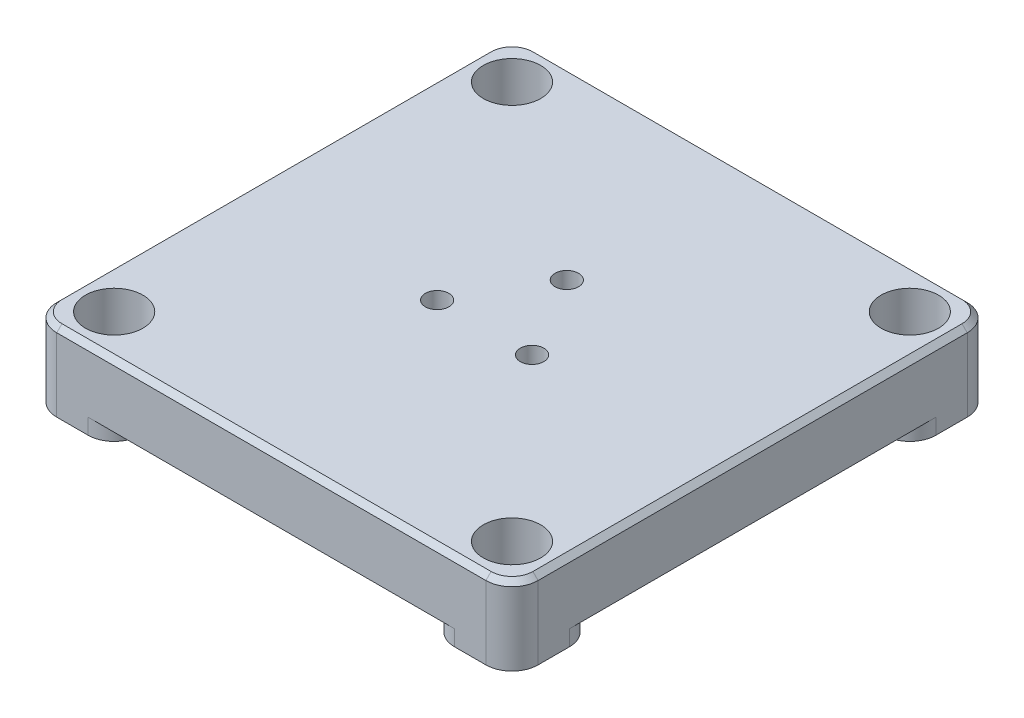
SolidWorks part; units mm, degrees
ref_plane "Спереди" through (0, 0, 0) normal (0, 0, 1) x (1, 0, 0)
ref_plane "Сверху" through (0, 0, 0) normal (0, 1, 0) x (1, 0, 0)
ref_plane "Справа" through (0, 0, 0) normal (1, 0, 0) x (0, 0, -1)
sketch "Эскиз1" plane through (0, 0, 0) normal (0, 1, 0) x (1, 0, 0)
  line L1 (-46.1, 46.1) -> (46.1, 46.1)
  line L2 (-46.1, 46.1) -> (-46.1, -46.1)
  line L3 (-46.1, -46.1) -> (46.1, -46.1)
  line L4 (46.1, 46.1) -> (46.1, -46.1)
  line L5 (-46.1, 46.1) -> (46.1, -46.1) construction
  line L6 (-46.1, -46.1) -> (46.1, 46.1) construction
  line L7 (38.1, 38.1) -> (-38.1, 38.1) construction
  line L8 (38.1, 38.1) -> (38.1, -38.1) construction
  line L9 (38.1, -38.1) -> (-38.1, -38.1) construction
  line L10 (-38.1, 38.1) -> (-38.1, -38.1) construction
  line L11 (38.1, 38.1) -> (-38.1, -38.1) construction
  line L12 (38.1, -38.1) -> (-38.1, 38.1) construction
  circle A0 centre (0, 0) radius 10.5 construction
  circle A1 centre (0, 10.5) radius 2.25
  circle A2 centre (-38.1, 38.1) radius 3.5
  circle A3 centre (38.1, 38.1) radius 3.5
  circle A4 centre (38.1, -38.1) radius 3.5
  circle A5 centre (-38.1, -38.1) radius 3.5
  circle A6 centre (9.0933, -5.25) radius 2.25
  circle A7 centre (-9.0933, -5.25) radius 2.25
  point P0 (0, 0)
  point P6 (0, 0)
  dimension "D4" = 21
  dimension "D5" = 4.5
  dimension "D6" = 7
  dimension "D7" = 7
  dimension "D8" = 7
  dimension "D9" = 7
  dimension "D1" = 92.2
  dimension "D2" = 92.2
  dimension "D3" = 76.2
  dimension "D10" = 3
extrude "Бобышка-Вытянуть1" add sketch "Эскиз1" along normal blind 12
sketch "Эскиз2" plane through (0, 0, 0) normal (0, -1, 0) x (1, 0, 0)
  circle A0 centre (-9.0933, 5.25) radius 3.6
  circle A1 centre (9.0933, 5.25) radius 3.6
  circle A2 centre (0, -10.5) radius 3.6
  dimension "D1" = 7.2
  dimension "D2" = 7.2
  dimension "D3" = 7.2
extrude "Вырез-Вытянуть1" cut sketch "Эскиз2" against normal offset from surface (2 mm away) 10 up to face at (9.0933, 12, 7.5)
sketch "Эскиз3" plane through (0, 0, 0) normal (0, -1, 0) x (1, 0, 0)
  line L0 (30.1, 30.1) -> (46.1, 30.1)
  line L1 (-30.1, 30.1) -> (-46.1, 30.1)
  line L2 (-30.1, 30.1) -> (-30.1, 46.1)
  line L3 (-30.1, 46.1) -> (-46.1, 46.1)
  line L4 (-46.1, 30.1) -> (-46.1, 46.1)
  line L5 (-30.1, 30.1) -> (-46.1, 46.1) construction
  line L6 (-30.1, 46.1) -> (-46.1, 30.1) construction
  line L7 (30.1, 30.1) -> (30.1, 46.1)
  line L8 (30.1, 46.1) -> (46.1, 46.1)
  line L9 (46.1, 30.1) -> (46.1, 46.1)
  line L10 (30.1, -30.1) -> (30.1, -46.1)
  line L11 (30.1, -30.1) -> (46.1, -30.1)
  line L12 (46.1, -30.1) -> (46.1, -46.1)
  line L13 (30.1, -46.1) -> (46.1, -46.1)
  line L14 (-30.1, -30.1) -> (-46.1, -30.1)
  line L15 (-30.1, -30.1) -> (-30.1, -46.1)
  line L16 (-30.1, -46.1) -> (-46.1, -46.1)
  line L17 (-46.1, -30.1) -> (-46.1, -46.1)
  line L18 (46.1, 46.1) -> (46.1, -46.1) construction
  line L19 (-46.1, 46.1) -> (46.1, 46.1) construction
  circle A0 centre (-38.1, 38.1) radius 3.5
  circle A1 centre (38.1, 38.1) radius 3.5
  circle A2 centre (38.1, -38.1) radius 3.5
  circle A3 centre (-38.1, -38.1) radius 3.5
  circle A4 centre (38.1, 38.1) radius 3.5 construction
  point P0 (-38.1, 38.1)
  dimension "D1" = 4
  dimension "D2" = 4
extrude "Бобышка-Вытянуть2" add sketch "Эскиз3" along normal blind 3
sketch "Эскиз4" plane through (0, 12, 0) normal (0, 1, 0) x (1, 0, 0)
  circle A0 centre (38.1, 38.1) radius 5.5
  circle A1 centre (38.1, -38.1) radius 5.5
  circle A2 centre (-38.1, -38.1) radius 5.5
  circle A3 centre (-38.1, 38.1) radius 5.5
  circle A4 centre (-38.1, 38.1) radius 3.5 construction
  dimension "D1" = 11
  dimension "D2" = 4
extrude "Вырез-Вытянуть2" cut sketch "Эскиз4" against normal offset from surface (10.8 mm away) 4.2 up to face at (38.1, -3, -38.1)
fillet "Скругление1" radius 5 16 edges at (-30.1, -1.5, 46.1) (-46.1, -1.5, 30.1) (-46.1, -1.5, -30.1) (-30.1, -1.5, -46.1) (30.1, -1.5, -46.1) (46.1, -1.5, -30.1) (46.1, -1.5, 30.1) (30.1, -1.5, 46.1) (-30.1, -1.5, 30.1) (30.1, -1.5, 30.1) (30.1, -1.5, -30.1) (-30.1, -1.5, -30.1) (-46.1, 4.5, -46.1) (46.1, 4.5, -46.1) (-46.1, 4.5, 46.1) (46.1, 4.5, 46.1)
chamfer "Фаска1" distance 1 angle 45 8 edges at (0, 12, -46.1) (-44.6355, 12, -44.6355) (44.6355, 12, -44.6355) (-46.1, 12, 0) (46.1, 12, 0) (-44.6355, 12, 44.6355) (44.6355, 12, 44.6355) (0, 12, 46.1)
equation "\"motor_diameter\"= 30"
equation "\"mm_diameter\"= IIF ( \"motor_diameter\" < 34 , 41 , \"motor_diameter\" + 8 )"
equation "\"upper_shafts_diameter\"= 5"
equation "\"upper_shats_length\"= 180"
equation "\"upper_bearing_d1\"= 10"
equation "\"upper_bearing_d2\"= 5"
equation "\"upper_bearing_h\"= 15"
equation "\"lower_shafts_diameter\"= 5"
equation "\"lower_shafts_length\"= 180"
equation "\"lower_bearing_d1\"= 10"
equation "\"lower_bearing_d2\"= 5"
equation "\"lower_bearing_h\"= 15"
equation "\"print_offset\"= 0.5"
equation "\"bh_screws_d\"= 2"
equation "\"bh_screws_h\"= 20"
equation "\"bh_screws_hh_d\"= 3.4"
equation "\"bh_screws_hh_h\"= 2"
equation "\"bh_nut_d\"= 3.8"
equation "\"bh_nut_h\"= 2"
equation "\"motor_screws_d\"= 3"
equation "\"motor_screws_h\"= 16"
equation "\"motor_screws_hh_d\"= 5.5"
equation "\"motor_screws_hh_h\"= 3"
equation "\"plate_hole_distance\"= 25.4"
equation "\"plate_screws_d\"= 6.5"
equation "\"shafts_diameter\"= IIF ( \"mm_diameter\" < 42 , 42 + 8 , \"mm_diameter\" + 8 )"
equation "\"central_hole_diameter\"= 8"
equation "\"bh_thikness\"= 4"
equation "\"ends_screws_d\"= 4"
equation "\"ends_screws_h\"= 16"
equation "\"ends_screws_hh_d\"= 6.7"
equation "\"ends_screws_hh_h\"= 4.1"
equation "\"ends_nut_d\"= 6.8"
equation "\"ends_nut_h\"= 3"
equation "\"D1@Эскиз1\"=\"D3@Эскиз1\"+16"
equation "\"D2@Эскиз1\"=\"D1@Эскиз1\""
equation "\"D3@Эскиз1\"=\"plate_hole_distance\"*3"
equation "\"D5@Эскиз1\"=\"ends_screws_d\"+\"print_offset\""
equation "\"D6@Эскиз1\"=\"plate_screws_d\"+\"print_offset\""
equation "\"D7@Эскиз1\"=\"D6@Эскиз1\""
equation "\"D8@Эскиз1\"=\"D6@Эскиз1\""
equation "\"D9@Эскиз1\"=\"D6@Эскиз1\""
equation "\"D1@Эскиз2\"=\"ends_screws_hh_d\"+\"print_offset\""
equation "\"D2@Эскиз2\"=\"D1@Эскиз2\""
equation "\"D3@Эскиз2\"=\"D1@Эскиз2\""
equation "\"D1@Вырез-Вытянуть1\"=\"ends_screws_h\"-6"
